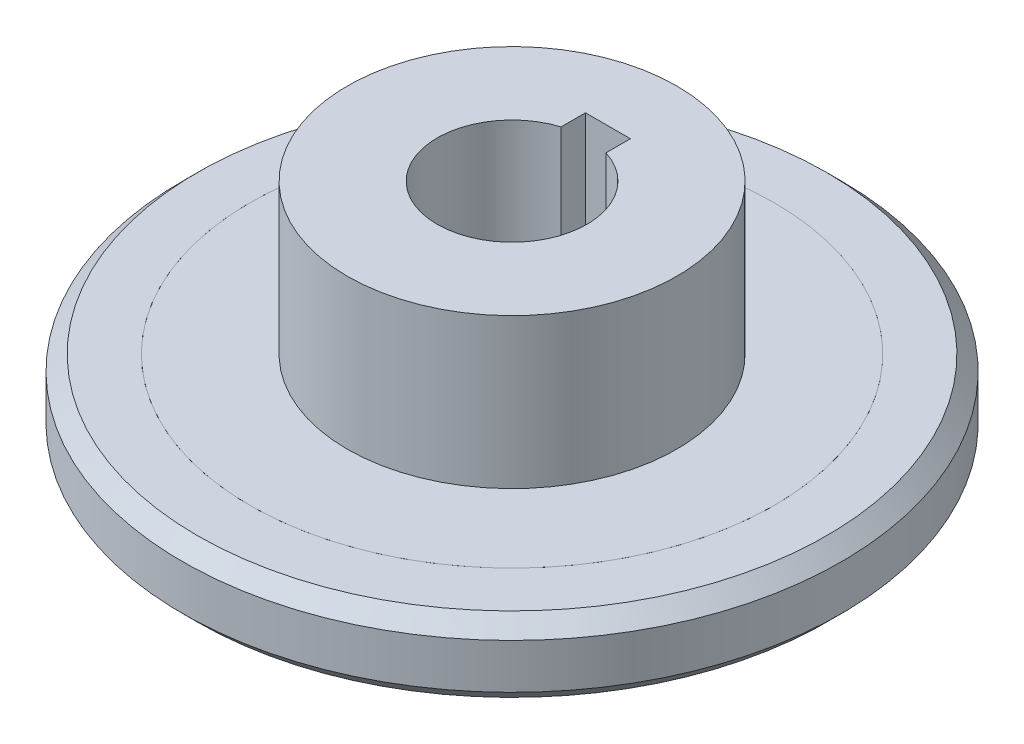
SolidWorks part; units mm, degrees
ref_plane "Front" through (0, 0, 0) normal (0, 0, 1) x (1, 0, 0)
ref_plane "Top" through (0, 0, 0) normal (0, 1, 0) x (1, 0, 0)
ref_plane "Right" through (0, 0, 0) normal (1, 0, 0) x (0, 0, -1)
sketch "Эскиз1" plane through (0, 0, 0) normal (0, 0, 1) x (1, 0, 0)
  line L0 (0, 0) -> (0, 6.9221) construction
  line L1 (5, 15) -> (5, 0)
  line L2 (5, 0) -> (17.5, 0)
  line L3 (17.5, 0) -> (17.5, 5)
  line L4 (17.5, 5) -> (11, 5)
  line L5 (11, 5) -> (11, 15)
  line L6 (11, 15) -> (5, 15)
  line L7 (0, 5) -> (0, 15) construction
  dimension "D1" = 35
  dimension "D2" = 10
  dimension "D3" = 5
  dimension "D5" = 22
revolve "Повернуть1" add sketch "Эскиз1" angle 360 about L0
sketch "Эскиз2" plane through (0, 0, 0) normal (0, 0, 1) x (1, 0, 0)
  line L3 (1.5, -27.4214) -> (-1.5, -27.4214)
  line L4 (1.5, -27.4214) -> (1.5, 27.4214)
  line L5 (1.5, 27.4214) -> (-1.5, 27.4214)
  line L6 (-1.5, -27.4214) -> (-1.5, 27.4214)
  line L7 (1.5, -27.4214) -> (-1.5, 27.4214) construction
  line L8 (1.5, 27.4214) -> (-1.5, -27.4214) construction
  point P0 (0, 0)
  dimension "D1" = 3
extrude "Вырез-Вытянуть1" cut sketch "Эскиз2" against normal blind 6.4
sketch "Эскиз3" plane through (0, 0, 0) normal (0, 0, 1) x (1, 0, 0)
  line L0 (0, 0) -> (0, 23.7771) construction
  line L1 (17.5, 0) -> (17.5, 5)
  line L2 (17.5, 0) -> (17.5, 5) construction
  line L3 (17.5, 5) -> (21, 5)
  line L6 (21, 5) -> (22, 4)
  line L7 (21, 0) -> (22, 1)
  line L8 (22, 1) -> (22, 4)
  line L11 (21, 0) -> (17.5, 0)
  line L12 (-17.5, 0) -> (17.5, 0) construction
  dimension "D1" = 45
  dimension "D2" = 1
  dimension "D3" = 44
revolve "Повернуть-Тонкостенный1" add sketch "Эскиз3" angle 360 about L0 wall 0.0001
sketch "Эскиз4" plane through (0, 5, 0) normal (0, 1, 0) x (1, 0, 0)
  circle A0 centre (-16.25, 0) radius 1.5
  circle A1 centre (16.25, 0) radius 1.5
  circle A2 centre (0, 0) radius 16.25 construction
  circle A3 centre (0, 0) radius 16.25 construction
  dimension "D3" = 3
extrude "Вырез-Вытянуть2" [suppressed] cut sketch "Эскиз4" against normal through all
